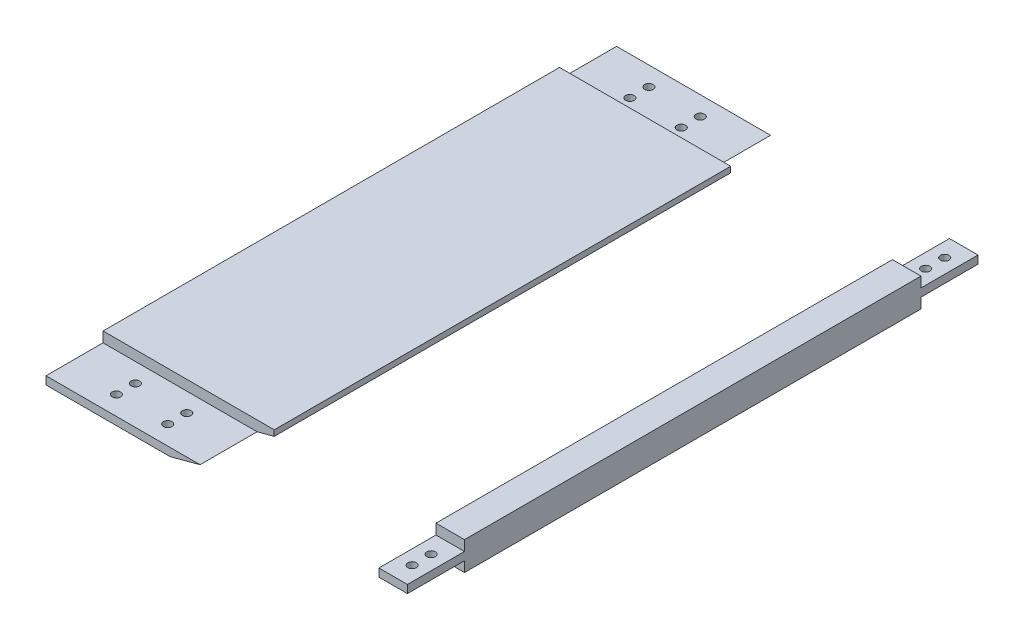
SolidWorks part; units mm, degrees
ref_plane "Ebene vorne" through (0, 0, 0) normal (0, 0, 1) x (1, 0, 0)
ref_plane "Ebene oben" through (0, 0, 0) normal (0, 1, 0) x (1, 0, 0)
ref_plane "Ebene rechts" through (0, 0, 0) normal (1, 0, 0) x (0, 0, -1)
sketch "Skizze1" plane through (0, 0, 0) normal (0, 0, 1) x (1, 0, 0)
  line L0 (-43.343, 0) -> (-28.343, 4)
  line L1 (-28.343, 4) -> (-28.343, 5)
  line L2 (-28.343, 5) -> (-58.343, 5)
  line L3 (-58.343, 5) -> (-58.343, 0)
  line L4 (-58.343, 0) -> (-43.343, 0)
  line L5 (0, 5) -> (0, 0)
  line L6 (0, 0) -> (5, 0)
  line L7 (5, 0) -> (5, 5)
  line L8 (5, 5) -> (0, 5)
  dimension "D1" = 30
  dimension "D2" = 1
  dimension "D3" = 15
  dimension "D4" = 5
  dimension "D5" = 5
  dimension "D6" = 5
  dimension "D7" = 5
extrude "Aufsatz-Linear austragen1" add sketch "Skizze1" along normal blind 100
sketch "Skizze3" plane through (0, 0, 0) normal (0, 0, -1) x (-1, 0, 0)
  line L0 (58.343, 5) -> (58.343, 0) construction
  line L1 (-5, 5) -> (58.343, 5)
  line L2 (-5, 5) -> (-5, 3.2)
  line L3 (-5, 3.2) -> (58.343, 3.2)
  line L4 (58.343, 5) -> (58.343, 3.2)
  line L5 (-5, 0) -> (-5, 5) construction
  line L6 (58.343, 0) -> (-5, 0)
  line L7 (58.343, 0) -> (58.343, 1.8)
  line L8 (58.343, 1.8) -> (-5, 1.8)
  line L9 (-5, 0) -> (-5, 1.8)
  dimension "D1" = 1.4
extrude "Schnitt-Linear austragen2" cut sketch "Skizze3" against normal blind 10
extrude "Schnitt-Linear austragen3" cut sketch "Skizze3<3>" against normal blind 10 from offset 90 offset against normal yes
sketch "Skizze3<3>" plane through (0, 0, 0) normal (0, 0, -1) x (-1, 0, 0) same geometry as "Skizze3"
sketch "Skizze4" plane through (0, 5, 0) normal (0, 1, 0) x (1, 0, 0)
  line L0 (-58.343, -3.3333) -> (5, -3.3333) construction
  line L1 (-58.343, -10) -> (-58.343, 0) construction
  line L2 (5, -10) -> (5, 0) construction
  line L3 (5, -3.3333) -> (5, -6.6667) construction
  line L4 (5, -6.6667) -> (-58.343, -6.6667) construction
  line L5 (-31.343, 0) -> (-31.343, -10) construction
  line L6 (-58.2737, 0) -> (-58.2737, -3.3333)
  line L7 (-58.343, 0) -> (5, 0)
  line L8 (-58.343, 0) -> (-58.343, -10)
  line L9 (-58.343, -10) -> (5, -10)
  line L10 (5, 0) -> (5, -10)
  line L11 (-58.0941, -3.3333) -> (-58.0941, -6.6667)
  line L12 (-57.7555, -6.6667) -> (-57.7555, -10)
  line L13 (0, -10) -> (0, 0) construction
  circle A0 centre (-49.343, -3.3333) radius 0.75
  circle A1 centre (-49.343, -6.6667) radius 0.75
  circle A2 centre (-40.343, -3.3333) radius 0.75
  circle A3 centre (-40.343, -6.6667) radius 0.75
  circle A4 centre (2.5, -3.3333) radius 0.75
  circle A5 centre (2.5, -6.6667) radius 0.75
  dimension "D5" = 1.5
  dimension "D1" = 9
  dimension "D2" = 9
  dimension "D3" = 9
  dimension "D4" = 9
  dimension "D6" = 2.5
  dimension "D7" = 2.5
extrude "Schnitt-Linear austragen4" cut sketch "Skizze4" against normal up to surface (3.2 mm away) contours A2 | A0 | A1 | A3 | A4 | A5 up to face at (-47.468, 1.8, 5)
pattern_linear "Lineares Muster1" count 2 spacing 90 along (0, 0, 1) of "Schnitt-Linear austragen4"
equation "\"1ß\"=12.3538"
